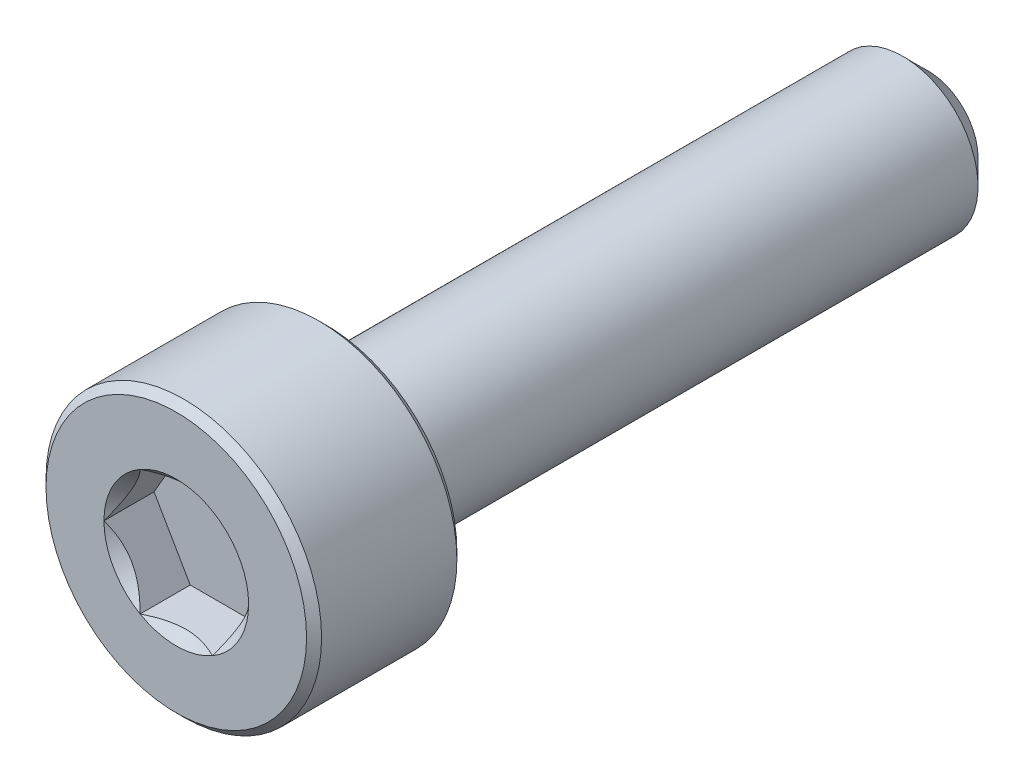
SolidWorks part; units mm, degrees
ref_plane "Front Plane" through (0, 0, 0) normal (0, 0, 1) x (1, 0, 0)
ref_plane "Top Plane" through (0, 0, 0) normal (0, 1, 0) x (1, 0, 0)
ref_plane "Right Plane" through (0, 0, 0) normal (1, 0, 0) x (0, 0, -1)
sketch "Sketch1" plane through (0, 0, 0) normal (1, 0, 0) x (0, 0, -1)
  line L0 (-7.5, 0) -> (7.5, 0) construction
  line L1 (7.5, 0) -> (7.5, 1) construction
  line L2 (7.5, 1) -> (7, 1.5) construction
  line L3 (7, 1.5) -> (-10.5, 1.5) construction
  line L5 (-4.5, 1.5) -> (-4.5, 2.75) construction
  line L6 (-4.5, 2.75) -> (-7.5, 2.75) construction
  line L7 (-7.5, 2.75) -> (-7.5, 0) construction
  line L8 (7.5, 1) -> (7.5, 1.5) construction
  line L9 (7.4688, 1.5541) -> (7.7187, 1.1211) construction
  line L10 (7.7187, 1.1211) -> (7.9688, 1.5541) construction
  line L11 (7.9688, 1.5541) -> (7.4688, 1.5541) construction
  line L12 (7.7188, 1.5541) -> (7.7187, 1.5) construction
  line L13 (7.7187, 1.1211) -> (7.7187, 1.1752) construction
  line L14 (7.6875, 1.1752) -> (7.75, 1.1752) construction
  line L15 (7.5, 1.5) -> (7.9375, 1.5) construction
  line L16 (7.4844, 1.5271) -> (7.9531, 1.5271) construction
  line L17 (7.5, 0) -> (7.5, -1.5) construction
  line L18 (-4.65, 2.75) -> (-4.5, 2.6) construction
  line L19 (-7.35, 2.75) -> (-7.5, 2.6) construction
  point P0 (-7.5, 1.25)
  point P3 (5.75, 1.5)
  point P4 (0, 0)
  point P22 (7.7187, 1.1752)
  point P24 (-10.5, 1.5)
  point P25 (7.7187, 1.5)
  point P28 (7.7188, 1.5271)
  point P29 (5.75, -1.5)
  point P31 (-6, 2.75)
  point P37 (-5.025, 2.75)
  point P38 (-7.275, 2.75)
  dimension "head height" = 3
  dimension "D1" = 45
  dimension "head dia" = 5.5
  dimension "thread dia" = 3
  dimension "drive size" = 2.5
  dimension "pitch" = 0.5
  dimension "D2" = 0.0625
  dimension "D3" = 0.5
  dimension "D4" = 1.75
  dimension "D7" = 0.15
  dimension "D8" = 0.15
  dimension "D9" = 0.15
  dimension "D10" = 0.075
  dimension "D11" = 0.375
  dimension "D12" = 18
  dimension "length" = 12
sketch "Sketch2" plane through (0, 0, 0) normal (1, 0, 0) x (0, 0, -1)
  line L1 (-7.35, 2.75) -> (-4.65, 2.75)
  line L4 (7, 1.5) -> (7.5, 1)
  line L5 (7.5, 1) -> (7.5, 0)
  line L6 (-4.65, 2.75) -> (-4.5, 2.6) construction
  line L7 (7.5, 0) -> (-7.5, 0)
  line L8 (-7.35, 2.75) -> (-7.5, 2.6) construction
  line L9 (-4.65, 2.75) -> (-4.5, 2.6)
  line L10 (-7.35, 2.75) -> (-7.5, 2.6)
  line L11 (-7.5, 2.6) -> (-7.5, 0)
  line L12 (-4.5, 2.6) -> (-4.5, 1.5)
  line L13 (-4.5, 1.5) -> (7, 1.5)
revolve "Revolve1" add sketch "Sketch2" angle 360 about L7
sketch "Sketch3" plane through (0, 0, 7.5) normal (0, 0, 1) x (1, 0, 0)
  line L1 (0.7217, 1.25) -> (-0.7217, 1.25)
  line L2 (-0.7217, 1.25) -> (-1.4434, 0)
  line L3 (-1.4434, 0) -> (-0.7217, -1.25)
  line L4 (-0.7217, -1.25) -> (0.7217, -1.25)
  line L5 (0.7217, -1.25) -> (1.4434, 0)
  line L6 (1.4434, 0) -> (0.7217, 1.25)
  circle A0 centre (0, 0) radius 1.25 construction
extrude "Cut-Extrude1" cut sketch "Sketch3" against normal offset from surface (1 mm away) 1 up to face at (-2.6, 0, 7.5)
sketch "Sketch4" plane through (0, 0, 7.5) normal (0, 0, 1) x (1, 0, 0)
  circle A0 centre (0, 0) radius 1.4434
extrude "Cut-Extrude2" cut sketch "Sketch4" against normal blind 0.5 draft 45
ref_plane "Plane1" [suppressed] through (0, 0, 10.5) normal (0, 0, 1) x (1, 0, 0)
split "Split1" [suppressed] bodies to split 106
sketch "Sketch6" [suppressed] plane through (0, 0, -7.5) normal (0, 0, -1) x (-1, 0, 0)
  circle A0 centre (0, 0) radius 1.5
curve "Helix/Spiral1" [suppressed] pitch 0.5 height 12.5 turns 25
sketch "Sketch7" [suppressed] plane through (0, 0, 0) normal (1, 0, 0) x (0, 0, -1)
  line L0 (7.4844, 1.5271) -> (7.9531, 1.5271)
  line L1 (7.9531, 1.5271) -> (7.75, 1.1752)
  line L2 (7.75, 1.1752) -> (7.6875, 1.1752)
  line L3 (7.6875, 1.1752) -> (7.4844, 1.5271)
sweep "Cut-Sweep1" [suppressed] cut profiles "Sketch7" path "Helix/Spiral1"
sketch "Sketch8" [suppressed] plane through (0, 0, 4.5) normal (0, 0, -1) x (-1, 0, 0)
  circle A0 centre (0, 0) radius 1.5
extrude "Boss-Extrude1" [suppressed] add sketch "Sketch8" along normal through all draft 45
ref_plane "Plane2" [suppressed] through (0, 0, 6) normal (0, 0, 1) x (1, 0, 0)
sketch "Sketch9" [suppressed] plane through (0, 0, 6) normal (0, 0, 1) x (1, 0, 0)
  line L0 (0, 2.6125) -> (0.048, 2.7496)
  line L1 (0, 2.6125) -> (-0.048, 2.7496)
  line L2 (0, 2.75) -> (0, 0) construction
  line L3 (-0.048, 2.7496) -> (0, 0) construction
  line L4 (0, 0) -> (0.048, 2.7496) construction
  arc A0 (0.048, 2.7496) -> (-0.048, 2.7496) centre (0, 0) ccw
  circle A1 centre (0, 0) radius 2.6125 construction
  dimension "D1" = 5.5
  dimension "D2" = 5.225
  dimension "D3" = 2
extrude "Cut-Extrude4" [suppressed] cut sketch "Sketch9" against normal up to vertex and the other way up to vertex
pattern_circular "CirPattern2" [suppressed] count 175 over 360 about axis through (0, 0, 7.5) along (0, 0, -1) of bodies 113
equation "\"D2@Sketch1\"=\"pitch@Sketch1\"/8"
equation "\"D3@Sketch1\"=\"pitch@Sketch1\""
equation "\"D3@Helix/Spiral1\"=\"length@Sketch1\"+\"pitch@Sketch1\""
equation "\"D4@Helix/Spiral1\"=\"pitch@Sketch1\""
equation "\"D4@Sketch1\"=\"pitch@Sketch1\"*3.5"
equation "\"D7@Sketch1\"=\"head height@Sketch1\"*.05"
equation "\"D8@Sketch1\"=\"D7@Sketch1\""
equation "\"D9@Sketch1\"=\"D7@Sketch1\""
equation "\"D10@Sketch1\"=\"D7@Sketch1\"/2"
equation "\"D11@Sketch1\"=\"D10@Sketch1\"*5"
equation "\"D2@Sketch9\"=\"D1@Sketch9\"*.95"
equation "\"D1@CirPattern2\"= ( 360 / \"D3@Sketch9\" ) - 5"
